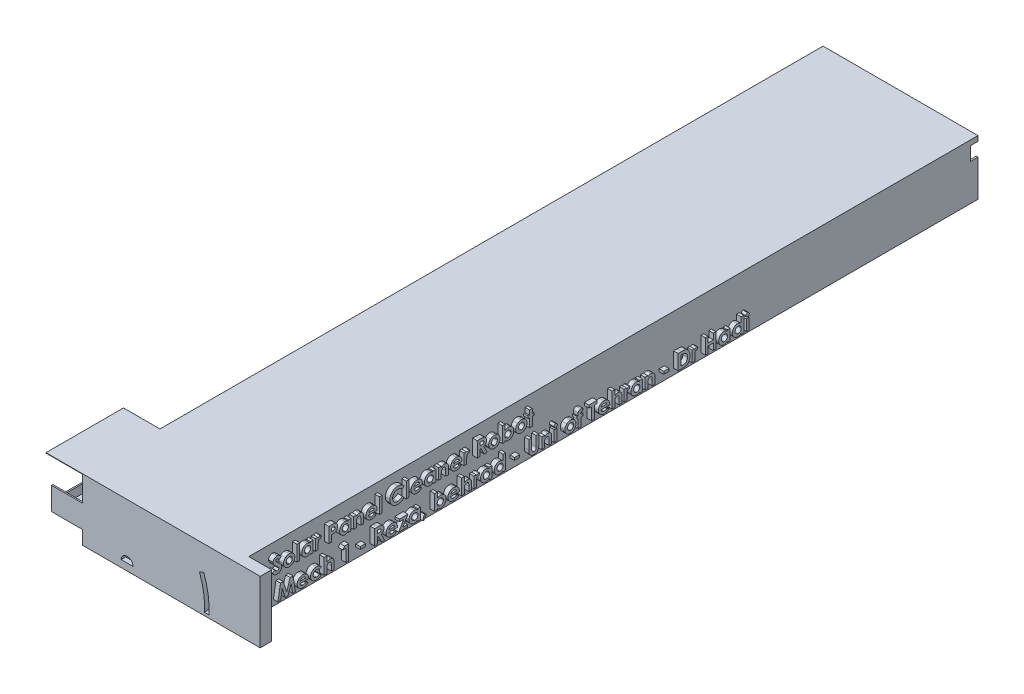
SolidWorks part; units mm, degrees
ref_plane "Front Plane" through (0, 0, 0) normal (0, 0, 1) x (1, 0, 0)
ref_plane "Top Plane" through (0, 0, 0) normal (0, 1, 0) x (1, 0, 0)
ref_plane "Right Plane" through (0, 0, 0) normal (1, 0, 0) x (0, 0, -1)
sketch "Sketch1" plane through (0, 0, 0) normal (0, 0, 1) x (1, 0, 0)
  line L0 (0, 0) -> (0, 121)
  line L1 (0, 121) -> (340, 121)
  line L2 (340, 121) -> (340, 0)
  line L3 (340, 0) -> (336, 0)
  line L4 (336, 0) -> (336, 117)
  line L5 (336, 117) -> (4, 117)
  line L6 (4, 117) -> (4, 0)
  line L7 (4, 0) -> (0, 0)
  dimension "D1" = 4
  dimension "D2" = 4
  dimension "D3" = 4
  dimension "D4" = 340
  dimension "D5" = 117
extrude "Boss-Extrude1" add sketch "Sketch1" along normal blind 1600
sketch "Sketch2" plane through (0, 0, 1600) normal (0, 0, 1) x (1, 0, 0)
  line L1 (0, 121) -> (340, 121)
  line L2 (0, 121) -> (0, 0)
  line L3 (0, 0) -> (340, 0)
  line L4 (340, 121) -> (340, 0)
extrude "Boss-Extrude2" add sketch "Sketch2" along normal blind 25
sketch "Sketch10" plane through (0, 0, 1625) normal (0, 0, 1) x (1, 0, 0)
  line L0 (340, 0) -> (340, 121) construction
  line L1 (0, 0) -> (340, 0)
  line L2 (0, 0) -> (0, -40)
  line L3 (0, -40) -> (340, -40)
  line L4 (340, 0) -> (340, -40)
  dimension "D1" = 40
extrude "Boss-Extrude4" add sketch "Sketch10" against normal blind 25
sketch "Sketch11" plane through (0, 0, 1625) normal (0, 0, 1) x (1, 0, 0)
  line L0 (0, -40) -> (340, -40) construction
  line L1 (340, 121) -> (390, 121)
  line L2 (340, 121) -> (340, -40)
  line L3 (340, -40) -> (390, -40)
  line L4 (390, 121) -> (390, -40)
  dimension "D1" = 50
extrude "Boss-Extrude5" add sketch "Sketch11" against normal blind 25
sketch "Sketch12" plane through (0, 0, 1600) normal (0, 0, -1) x (-1, 0, 0)
  line L0 (-340, 121) -> (-340, 0) construction
  line L1 (0, -40) -> (-390, -40) construction
  circle A0 centre (-363.9, 7) radius 13
  dimension "D2" = 47
  dimension "D3" = 26
  dimension "D1" = 23.9
extrude "Cut-Extrude1" cut sketch "Sketch12" against normal blind 5
sketch "Sketch13" plane through (0, 0, 1625) normal (0, 0, 1) x (1, 0, 0)
  line L0 (390, -40) -> (390, 121) construction
  line L1 (0, -40) -> (390, -40)
  line L2 (0, -40) -> (0, -15)
  line L3 (0, -15) -> (390, -15)
  line L4 (390, -40) -> (390, -15)
  dimension "D1" = 25
extrude "Cut-Extrude2" cut sketch "Sketch13" against normal blind 25
sketch "Sketch14" plane through (340, 0, 0) normal (1, 0, 0) x (0, 0, -1)
  line L0 (0, 0) -> (0, 121) construction
  line L1 (0, 110) -> (-17, 110)
  line L2 (0, 110) -> (0, 80)
  line L3 (0, 80) -> (-17, 80)
  line L4 (-17, 110) -> (-17, 80)
  line L5 (-1600, 0) -> (0, 0) construction
  dimension "D1" = 30
  dimension "D2" = 17
  dimension "D3" = 80
extrude "Cut-Extrude3" cut sketch "Sketch14" against normal blind 5
sketch "Sketch16" plane through (0, 0, 1625) normal (0, 0, 1) x (1, 0, 0)
  line L1 (0, 121) -> (0, -15) construction
  line L2 (390, 121) -> (0, 121) construction
  circle A0 centre (97.85, 0.18) radius 13
  dimension "D1" = 120.82
  dimension "D2" = 26
  dimension "D3" = 97.85
extrude "Cut-Extrude4" cut sketch "Sketch16" against normal blind 25
sketch "Sketch17" plane through (0, 0, 1625) normal (0, 0, 1) x (1, 0, 0)
  line L1 (84.85, 0.18) -> (110.85, 0.18)
  line L2 (84.85, 0.18) -> (84.85, -12.82)
  line L3 (84.85, -12.82) -> (110.85, -12.82)
  line L4 (110.85, 0.18) -> (110.85, -12.82)
  line L5 (390, 121) -> (0, 121) construction
  circle A0 centre (97.85, 0.18) radius 13 construction
  dimension "D1" = 13
  dimension "D2" = 26
  dimension "D3" = 120.82
extrude "Boss-Extrude6" add sketch "Sketch17" against normal blind 10
sketch "Sketch18" plane through (0, 0, 1600) normal (0, 0, -1) x (-1, 0, 0)
  line L0 (-390, -15) -> (-390, 121) construction
  line L1 (-363.9, 20) -> (-377, 20)
  line L2 (-363.9, 20) -> (-363.9, -6)
  line L3 (-363.9, -6) -> (-377, -6)
  line L4 (-377, 20) -> (-377, -6)
  circle A0 centre (-363.9, 7) radius 13 construction
  circle A1 centre (-363.9, 7) radius 13 construction
  dimension "D1" = 13.1
  dimension "D2" = 26
  dimension "D3" = 13
extrude "Boss-Extrude8" add sketch "Sketch18" along normal blind 2
sketch "Sketch19" plane through (0, 0, 1598) normal (0, 0, -1) x (-1, 0, 0)
  line L0 (-363.9, -6) -> (-363.9, 20) construction
  circle A0 centre (-363.9, 7) radius 8.575
  dimension "D1" = 17.15
extrude "Cut-Extrude5" cut sketch "Sketch19" against normal blind 2
sketch "Sketch21" plane through (340, 0, 0) normal (1, 0, 0) x (0, 0, -1)
  text T0 "<b>Solar Panel Cleaner Robot</b>\r\n<b> Mech 1 - Reza, behrad - Uni of Tehran - Dr Hadi</b>" font "Century Gothic" height 33
extrude "Boss-Extrude9" add sketch "Sketch21" along normal blind 10
sketch "Sketch27" plane through (0, 0, 1625) normal (0, 0, 1) x (1, 0, 0)
  line L0 (0, 18) -> (-65, 18)
  line L1 (0, 121) -> (0, -15) construction
  line L2 (-65, 18) -> (-65, 37)
  line L3 (-65, 37) -> (-68, 37)
  line L4 (-68, 37) -> (-68, 19.3192)
  line L5 (-68, 19.3192) -> (-68, 15)
  line L6 (-68, 15) -> (0, 15)
  line L7 (0, 15) -> (0, 18)
  line L8 (390, -15) -> (0, -15) construction
  dimension "D1" = 3
  dimension "D2" = 3
  dimension "D3" = 30
  dimension "D4" = 65
  dimension "D5" = 22
extrude "Boss-Extrude10" add sketch "Sketch27" against normal blind 170
sketch "Sketch28" plane through (-68, 0, 0) normal (-1, 0, 0) x (0, 0, 1)
  line L0 (1455, 37) -> (1625, 37) construction
  line L1 (1455, 15) -> (1458, 15)
  line L2 (1455, 15) -> (1455, 37)
  line L3 (1455, 37) -> (1458, 37)
  line L4 (1458, 15) -> (1458, 37)
  dimension "D1" = 3
extrude "Boss-Extrude11" add sketch "Sketch28" against normal blind 70
sketch "Sketch29" plane through (-68, 0, 0) normal (-1, 0, 0) x (0, 0, 1)
  line L0 (1455, 15) -> (1625, 15) construction
  line L1 (1622, 15) -> (1625, 15)
  line L2 (1622, 15) -> (1622, 65)
  line L3 (1622, 65) -> (1625, 65)
  line L4 (1625, 15) -> (1625, 65)
  line L5 (1625, 121) -> (1625, 18) construction
  dimension "D1" = 3
  dimension "D2" = 50
extrude "Boss-Extrude12" add sketch "Sketch29" against normal blind 70
sketch "Sketch30" plane through (0, 0, 0) normal (-1, 0, 0) x (0, 0, 1)
  line L0 (1455, 37) -> (1455, 15) construction
  line L1 (1625, 121) -> (1455, 121)
  line L2 (1625, 121) -> (1625, 120)
  line L3 (1625, 120) -> (1455, 120)
  line L4 (1455, 121) -> (1455, 120)
  dimension "D1" = 1
  dimension "D2" = 0
extrude "Boss-Extrude13" add sketch "Sketch30" along normal blind 80
sketch "Sketch33" plane through (0, 0, 1625) normal (0, 0, 1) x (1, 0, 0)
  arc A0 (272.6304, -8.4932) -> (261.3357, 64.6865) centre (97.9, 2) ccw
extrude "Cut-Extrude-Thin1" cut sketch "Sketch33" against normal blind 50 and the other way through all thin thin type mid plane wall 10
sketch "Sketch34" plane through (336, 0, 0) normal (-1, 0, 0) x (0, 0, 1)
  line L0 (1553.29, 0) -> (1553.29, 32)
  line L1 (1600, 0) -> (0, 0) construction
  line L2 (1553.29, 32) -> (1572.29, 32)
  line L3 (1572.29, 32) -> (1572.29, -1.5)
  line L4 (1572.29, -1.5) -> (1553.29, -1.5)
  line L5 (1553.29, -1.5) -> (1553.29, 0)
  dimension "D1" = 19
  dimension "26" = 32
extrude "Cut-Extrude6" cut sketch "Sketch34" against normal blind 20
sketch "Sketch35" plane through (0, 0, 1600) normal (0, 0, -1) x (-1, 0, 0)
  line L0 (-4, 15.8635) -> (-47.6283, 15.8635)
  line L1 (-4, 0) -> (-4, 117) construction
  line L5 (-47.6283, 15.8635) -> (-81.5351, 15.8635)
  line L6 (-81.5351, 15.8635) -> (-83.3282, 15.8635)
extrude "Extrude-Thin1" add sketch "Sketch35" along normal blind 30 thin thin type one direction wall 2
